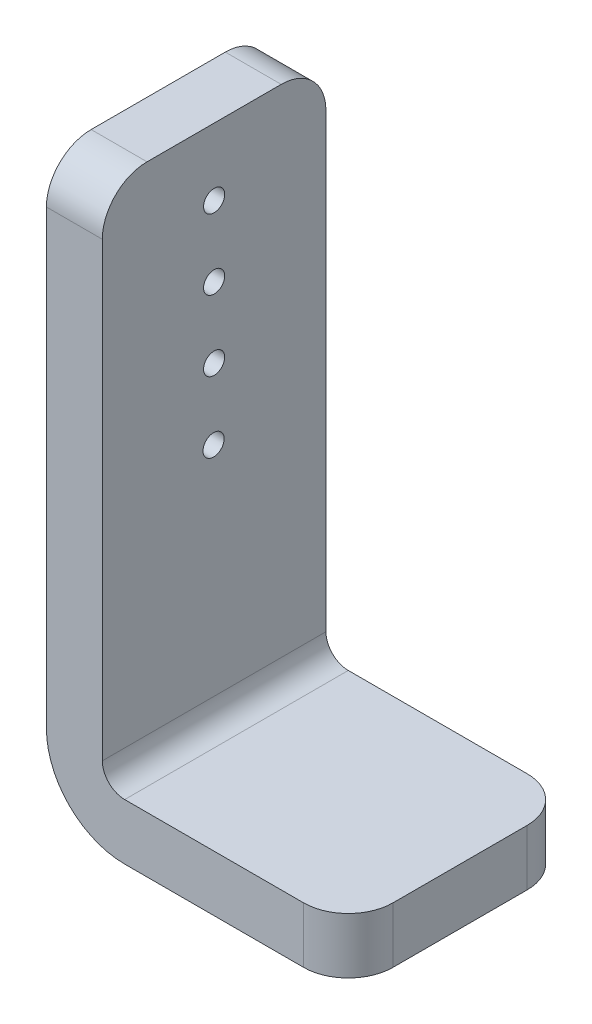
SolidWorks part; units mm, degrees
material "6061 Alloy"
ref_plane "Front Plane" through (0, 0, 0) normal (0, 0, 1) x (1, 0, 0)
ref_plane "Top Plane" through (0, 0, 0) normal (0, 1, 0) x (1, 0, 0)
ref_plane "Right Plane" through (0, 0, 0) normal (1, 0, 0) x (0, 0, -1)
sketch "Sketch1" plane through (0, 0, 0) normal (0, 0, 1) x (1, 0, 0)
  line L0 (0, 16.4759) -> (0, -11.7181)
  line L1 (1.27, -12.9881) -> (13.97, -12.9881)
  line L2 (-3.175, 16.4759) -> (-3.175, -11.7181)
  line L3 (1.27, -16.1631) -> (13.97, -16.1631)
  line L4 (0, 16.4759) -> (-3.175, 16.4759)
  line L5 (13.97, -12.9881) -> (13.97, -16.1631)
  arc A0 (1.27, -12.9881) -> (0, -11.7181) centre (1.27, -11.7181) cw
  arc A1 (1.27, -16.1631) -> (-3.175, -11.7181) centre (1.27, -11.7181) cw
  dimension "D1" = 1.27
  dimension "D3" = 12.7
  dimension "D4" = 28.194
  dimension "D2" = 3.175
extrude "Boss-Extrude1" add sketch "Sketch1" along normal blind 12.7
sketch "Sketch2" plane through (-3.175, 0, 0) normal (-1, 0, 0) x (0, 0, 1)
  line L0 (12.7, 16.4759) -> (0, 16.4759) construction
  line L1 (12.7, 16.4759) -> (0, 16.4759) construction
  line L2 (6.35, 12.6659) -> (2.9, 12.6659)
  line L6 (3.7, 10.4568) -> (4.353, -1.4933)
  line L7 (9, 10.4568) -> (8.347, -1.4933)
  arc A6 (9, 10.4568) -> (3.7, 10.4568) centre (6.35, 12.6659) ccw
  arc A7 (4.353, -1.4933) -> (8.347, -1.4933) centre (6.35, -1.3841) ccw
  circle A8 centre (6.3809, 0.6659) radius 0.6
  circle A11 centre (6.35, 4.6659) radius 0.6
  circle A15 centre (6.35, 8.6659) radius 0.6
  circle A17 centre (6.35, 12.6659) radius 0.6
  point P13 (6.35, 16.4759)
  dimension "D1" = 6.9
  dimension "D2" = 4
  dimension "D7" = 1.2
  dimension "D8" = 4
  dimension "D3" = 11.95
  dimension "D4" = 0.653
  dimension "D5" = 5.3
  dimension "D6" = 3.994
  dimension "D9" = 4
  dimension "D11" = 4
  dimension "D12" = 3.81
extrude "Cut-Extrude1" cut sketch "Sketch2" against normal up to next from surface contours A17 | A15 | A11 | A8 starting at face at (-3.175, 2.3789, 6.35)
sketch "Sketch3" plane through (-3.175, 0, 0) normal (-1, 0, 0) x (0, 0, 1)
  line L0 (6.35, 16.4759) -> (6.35, -11.7181)
  line L1 (12.7, 16.4759) -> (0, 16.4759) construction
  line L2 (12.7, -11.7181) -> (0, -11.7181) construction
fillet "Fillet1" radius 2.54 4 edges at (13.97, -14.5756, 0) (13.97, -14.5756, 12.7) (-1.5875, 16.4759, 0) (-1.5875, 16.4759, 12.7)
